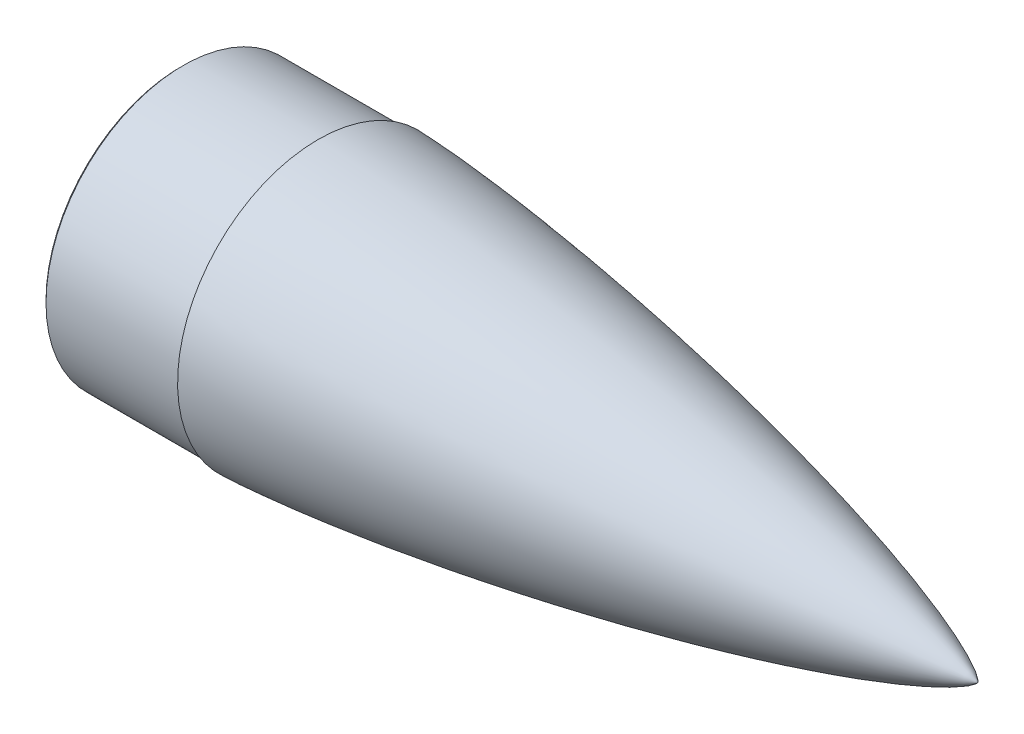
SolidWorks part; units mm, degrees
material "Plain Carbon Steel"
ref_plane "Front Plane" through (0, 0, 0) normal (0, 0, 1) x (1, 0, 0)
ref_plane "Top Plane" through (0, 0, 0) normal (0, 1, 0) x (1, 0, 0)
ref_plane "Right Plane" through (0, 0, 0) normal (1, 0, 0) x (0, 0, -1)
ref_axis "Axis1" through (46.9179, 0, 0) along (-1, 0, 0)
sketch "Sketch10" plane through (0, 0, 0) normal (0, 0, 1) x (1, 0, 0)
  line L1 (-1.0327, 0) -> (486.9547, 0) construction
  line L2 (11.1125, 81.9998) -> (11.1125, 67.4998)
  line L3 (11.1125, 81.9998) -> (-84.6045, 81.9998)
  line L4 (408.9673, 0) -> (368.9673, 0)
  line L5 (-84.6045, 81.9998) -> (-84.6045, 84.9998)
  line L6 (-84.6045, 84.9998) -> (0.3953, 84.9998)
  line L7 (0.3953, 84.9998) -> (0.3953, 86.9998)
  line L8 (11.1125, 67.4998) -> (129.3045, 67.4998)
  spline S0 degree 4 poles (408.9673, 0) (408.9649, 0.0135) (408.958, 0.0399) (408.9365, 0.0905) (408.8922, 0.1741) (408.8263, 0.2756) (408.7217, 0.4158) (408.5611, 0.6051) (408.3056, 0.8724) (407.8697, 1.2753) (407.121, 1.8851) (405.8038, 2.8259) (403.4624, 4.2872) (399.3253, 6.5318) (392.4811, 9.7589) (380.6621, 14.628) (363.6372, 20.7117) (342.2152, 27.4765) (317.4285, 34.4976) (291.8793, 41.1048) (266.2105, 47.229) (240.4455, 52.9334) (214.5989, 58.2554) (188.6809, 63.2176) (165.9462, 67.2533) (146.422, 70.4938) (130.1279, 73.0449) (117.0786, 74.9942) (104.0155, 76.8485) (92.5733, 78.3845) (82.7571, 79.6356) (74.5713, 80.6322) (68.0193, 81.4008) (61.4637, 82.1394) (54.9047, 82.8464) (48.3422, 83.5199) (41.7761, 84.1578) (36.0275, 84.6822) (31.0979, 85.1052) (26.9883, 85.4387) (23.6997, 85.6932) (20.0858, 85.9584) (16.7199, 86.189) (13.6021, 86.387) (10.7327, 86.5546) (8.4366, 86.6787) (6.14, 86.7922) (4.1299, 86.8793) (2.4065, 86.9446) (1.2573, 86.979) (0.6827, 86.9949) (0.3953, 86.9998) knots 0 0 0 0 0 0.00013 0.00026 0.00052 0.0009 0.00128 0.001925 0.002882 0.004418 0.006927 0.011111 0.018279 0.030673 0.051704 0.083102 0.139909 0.202703 0.265496 0.32829 0.391083 0.453877 0.516671 0.579464 0.642258 0.673655 0.705051 0.736448 0.767845 0.799242 0.81494 0.830639 0.846337 0.862036 0.877734 0.893432 0.909131 0.924829 0.932678 0.940527 0.948377 0.956226 0.967169 0.972641 0.978113 0.983585 0.989056 0.994528 0.997264 1 1 1 1 1 construction
  spline S1 degree 4 poles (408.9673, 0) (408.9649, 0.0135) (408.958, 0.0399) (408.9365, 0.0905) (408.8922, 0.1741) (408.8263, 0.2756) (408.7217, 0.4158) (408.5611, 0.6051) (408.3056, 0.8724) (407.8697, 1.2753) (407.121, 1.8851) (405.8038, 2.8259) (403.4624, 4.2872) (399.3253, 6.5318) (392.4811, 9.7589) (380.6621, 14.628) (363.6372, 20.7117) (342.2152, 27.4765) (317.4285, 34.4976) (291.8793, 41.1048) (266.2105, 47.229) (240.4455, 52.9334) (214.5989, 58.2554) (188.6809, 63.2176) (165.9462, 67.2533) (146.422, 70.4938) (130.1279, 73.0449) (117.0786, 74.9942) (104.0155, 76.8485) (92.5733, 78.3845) (82.7571, 79.6356) (74.5713, 80.6322) (68.0193, 81.4008) (61.4637, 82.1394) (54.9047, 82.8464) (48.3422, 83.5199) (41.7761, 84.1578) (36.0275, 84.6822) (31.0979, 85.1052) (26.9883, 85.4387) (23.6997, 85.6932) (20.0858, 85.9584) (16.7199, 86.189) (13.6021, 86.387) (10.7327, 86.5546) (8.4366, 86.6787) (6.14, 86.7922) (4.1299, 86.8793) (2.4065, 86.9446) (1.2573, 86.979) (0.6827, 86.9949) (0.3953, 86.9998) knots 0 0 0 0 0 0.00013 0.00026 0.00052 0.0009 0.00128 0.001925 0.002882 0.004418 0.006927 0.011111 0.018279 0.030673 0.051704 0.083102 0.139909 0.202703 0.265496 0.32829 0.391083 0.453877 0.516671 0.579464 0.642258 0.673655 0.705051 0.736448 0.767845 0.799242 0.81494 0.830639 0.846337 0.862036 0.877734 0.893432 0.909131 0.924829 0.932678 0.940527 0.948377 0.956226 0.967169 0.972641 0.978113 0.983585 0.989056 0.994528 0.997264 1 1 1 1 1
  spline S2 degree 4 poles (368.9673, 0) (368.9653, 0.0123) (368.9594, 0.0365) (368.9406, 0.083) (368.9023, 0.1587) (368.8455, 0.2503) (368.7557, 0.3766) (368.6167, 0.5484) (368.3929, 0.7936) (368.0087, 1.1649) (367.3447, 1.7299) (366.1761, 2.6016) (364.0928, 3.96) (360.426, 6.0407) (354.4022, 9.0183) (344.043, 13.5077) (329.152, 19.1285) (310.4252, 25.3986) (288.7413, 31.9337) (266.3785, 38.1061) (243.9014, 43.8469) (221.332, 49.212) (198.684, 54.2345) (175.9669, 58.9343) (156.0346, 62.7717) (138.9133, 65.8645) (124.6221, 68.3077) (113.1754, 70.1797) (101.7151, 71.9664) (91.6754, 73.4517) (83.0615, 74.6659) (75.8775, 75.6363) (70.1269, 76.3867) (64.3728, 77.1101) (58.6152, 77.8049) (52.854, 78.4695) (47.0892, 79.1019) (42.0417, 79.6247) (37.7129, 80.0488) (34.1039, 80.385) (31.2157, 80.6428) (28.0648, 80.911) (24.6507, 81.1843) (21.4654, 81.4195) (18.5093, 81.6177) (16.0448, 81.767) (14.3191, 81.8612) (12.8395, 81.9336) (11.8527, 81.9739) (11.3593, 81.993) (11.1125, 81.9998) knots 0 0 0 0 0 0.000135 0.00027 0.00054 0.00092 0.001299 0.001947 0.002931 0.004512 0.007081 0.01138 0.018708 0.031424 0.052705 0.084103 0.14091 0.203703 0.266497 0.329291 0.392084 0.454878 0.517672 0.580465 0.643259 0.674656 0.706052 0.737449 0.768846 0.800243 0.815941 0.831639 0.847338 0.863036 0.878735 0.894433 0.910132 0.92583 0.933679 0.941528 0.949378 0.957227 0.96792 0.978613 0.98396 0.989307 0.994653 0.997327 1 1 1 1 1 construction
  spline S3 degree 4 poles (368.9673, 0) (368.9653, 0.0123) (368.9594, 0.0365) (368.9406, 0.083) (368.9023, 0.1587) (368.8455, 0.2503) (368.7557, 0.3766) (368.6167, 0.5484) (368.3929, 0.7936) (368.0087, 1.1649) (367.3447, 1.7299) (366.1761, 2.6016) (364.0928, 3.96) (360.426, 6.0407) (354.4022, 9.0183) (344.043, 13.5077) (329.152, 19.1285) (310.4252, 25.3986) (288.7413, 31.9337) (266.3785, 38.1061) (243.9014, 43.8469) (221.332, 49.212) (198.684, 54.2345) (175.9669, 58.9343) (156.0346, 62.7717) (141.5091, 65.3956) (132.6794, 66.9245) (129.5628, 67.4559) (129.3045, 67.4998) knots 0 0 0 0 0 0.000135 0.00027 0.00054 0.00092 0.001299 0.001947 0.002931 0.004512 0.007081 0.01138 0.018708 0.031424 0.052705 0.084103 0.14091 0.203703 0.266497 0.329291 0.392084 0.454878 0.517672 0.580465 0.643259 0.674656 0.677492 0.677492 0.677492 0.677492 0.677492
  dimension "D1" = 86.9998
  dimension "D2" = 3
  dimension "D3" = 410
  dimension "D4" = 84.9998
  dimension "D5" = 370
  dimension "D6" = 84.9998
  dimension "D7" = 19.5
  dimension "D8" = 118.192
revolve "Revolve1" add sketch "Sketch10" angle 360 about axis through (46.9179, 0, 0) along (-1, 0, 0)
chamfer "Chamfer1" distance 1.5 angle 45 1 edges at (-84.6045, 0, -84.9998)
ref_plane "Plane1" through (70, 0, 0) normal (1, 0, 0) x (0, 0, -1)
sketch "Sketch11" plane through (70, 0, 0) normal (1, 0, 0) x (0, 0, -1)
  line L0 (39.6458, -13.0184) -> (39.6458, 13.0184)
  line L1 (-13.0184, -39.6458) -> (-13.0184, -66.2327)
  line L2 (-13.0184, -39.6458) -> (13.0184, -39.6458)
  line L3 (39.6458, -13.0184) -> (66.2327, -13.0184)
  line L4 (39.6458, 13.0184) -> (66.2327, 13.0184)
  line L5 (13.0184, -39.6458) -> (13.0184, -66.2327)
  line L6 (-39.6458, 13.0184) -> (-66.2327, 13.0184)
  line L7 (-39.6458, 13.0184) -> (-39.6458, -13.0184)
  line L8 (-39.6458, -13.0184) -> (-66.2327, -13.0184)
  line L9 (13.0184, 39.6458) -> (13.0184, 66.2327)
  line L10 (13.0184, 39.6458) -> (-13.0184, 39.6458)
  line L11 (-13.0184, 39.6458) -> (-13.0184, 66.2327)
  circle A0 centre (0, 0) radius 67.5
  circle A1 centre (0, 0) radius 67.5
  circle A2 centre (0, 0) radius 67.5
  circle A3 centre (0, 0) radius 67.5
  circle A4 centre (0, 52.1458) radius 5
  circle A5 centre (0, 0) radius 67.5
  circle A6 centre (52.1458, 0) radius 5
  circle A7 centre (0, 0) radius 67.5
  circle A8 centre (0, -52.1458) radius 5
  circle A9 centre (0, 0) radius 67.5
  circle A10 centre (-52.1458, 0) radius 5
  point P26 (0, 0)
  point P39 (0, 0)
  dimension "D1" = 4
  dimension "D2" = 4
extrude "Boss-Extrude6" add sketch "Sketch11" along normal blind 7.5 and the other way blind 7.5 contours L9 A0 L11 L10 | L3 A0 L4 L0 | L1 A0 L5 L2 | L6 A0 L8 L7 region at (70, 0, -40.027) region at (70, -67.1187, 0) region at (70, 52.9392, -12.6371) region at (70, 0, 67.1187)
